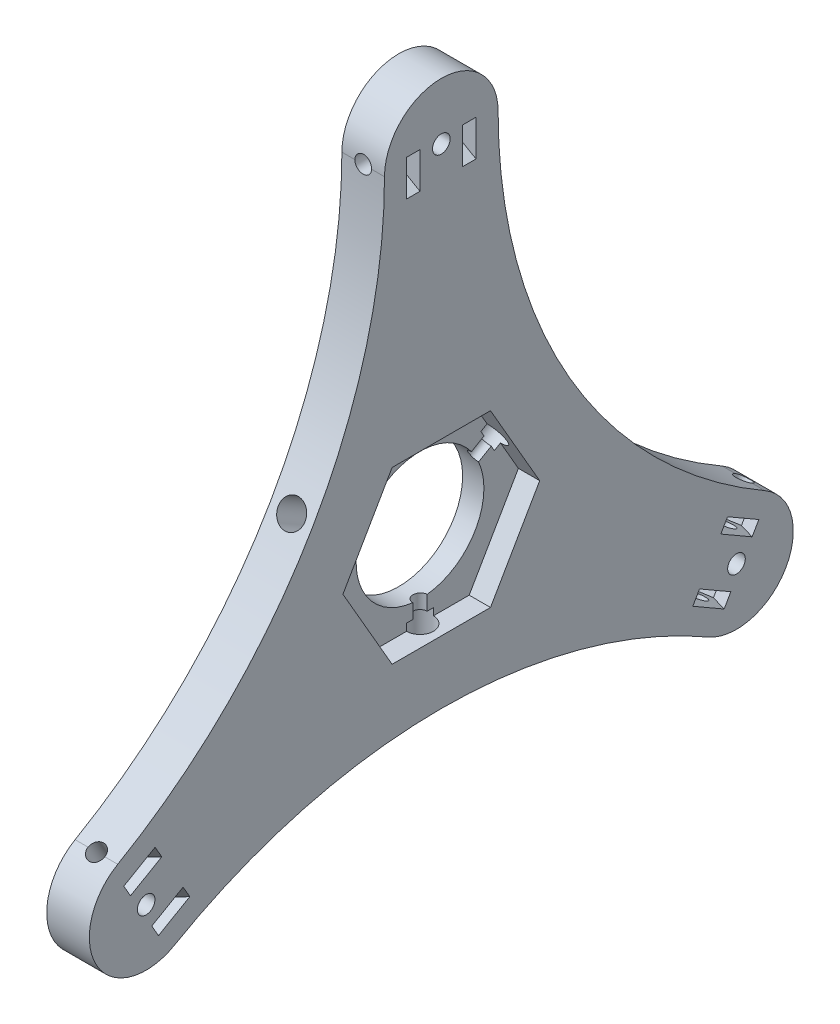
SolidWorks part; units mm, degrees
ref_plane "Front Plane" through (0, 0, 0) normal (0, 0, 1) x (1, 0, 0)
ref_plane "Top Plane" through (0, 0, 0) normal (0, 1, 0) x (1, 0, 0)
ref_plane "Right Plane" through (0, 0, 0) normal (1, 0, 0) x (0, 0, -1)
sketch "Sketch1" plane through (0, 0, 0) normal (1, 0, 0) x (0, 0, -1)
  line L0 (0, 0) -> (0, 76.2) construction
  line L1 (0, 0) -> (65.9911, -38.1) construction
  line L2 (0, 0) -> (-65.9911, -38.1) construction
  line L3 (-65.9911, -38.1) -> (0, 76.2) construction
  line L4 (0, 76.2) -> (65.9911, -38.1) construction
  line L5 (65.9911, -38.1) -> (-65.9911, -38.1) construction
  line L6 (-12.7, 76.2) -> (12.7, 76.2) construction
  line L8 (-3.6662, 6.35) -> (-7.3323, 0)
  line L9 (-7.3323, 0) -> (-3.6662, -6.35)
  line L10 (-3.6662, -6.35) -> (3.6662, -6.35)
  line L11 (3.6662, -6.35) -> (7.3323, 0)
  line L12 (7.3323, 0) -> (3.6662, 6.35)
  line L13 (3.6662, 6.35) -> (-3.6662, 6.35)
  circle A1 centre (0, 76.2) radius 1.9685
  circle A2 centre (65.9911, -38.1) radius 1.9685
  circle A3 centre (-65.9911, -38.1) radius 1.9685
  arc A4 (12.7, 76.2) -> (-12.7, 76.2) centre (0, 76.2) ccw
  arc A5 (59.6411, -49.0985) -> (72.3411, -27.1015) centre (65.9911, -38.1) ccw
  arc A6 (-72.3411, -27.1015) -> (-59.6411, -49.0985) centre (-65.9911, -38.1) ccw
  arc A7 (-12.7, 76.2) -> (-72.3411, -27.1015) centre (-131.9823, 76.2) cw
  arc A8 (12.7, 76.2) -> (72.3411, -27.1015) centre (131.9823, 76.2) ccw
  arc A9 (-59.6411, -49.0985) -> (59.6411, -49.0985) centre (0, -152.4) cw
  circle A10 centre (0, 0) radius 6.35 construction
  dimension "D1" = 12.7
  dimension "D2" = 3.937
  dimension "D4" = 25.4
  dimension "D3" = 76.2
extrude "Boss-Extrude1" add sketch "Sketch1" along normal blind 9.525 contours A6 A9 A5 A8 A4 A7 A1 A2 A3 region at (0, 15.5067, -26.8583)
sketch "Sketch3" plane through (0, 3.175, 5.4993) normal (0, -0.5, -0.866) x (-1, 0, 0)
  line L0 (-9.525, 0) -> (0, 0) construction
  line L4 (0, -3.6662) -> (0, 3.6662)
  line L5 (0, 3.6662) -> (-9.525, 3.6662)
  line L6 (-9.525, 3.6662) -> (-9.525, -3.6662)
  line L7 (-9.525, -3.6662) -> (0, -3.6662)
  line L8 (0, -3.6662) -> (0, 3.6662) construction
  line L9 (0, 3.6662) -> (-9.525, 3.6662) construction
  line L10 (-9.525, 3.6662) -> (-9.525, -3.6662) construction
  line L11 (-9.525, -3.6662) -> (0, -3.6662) construction
  circle A0 centre (-4.7625, 0) radius 1.6
  dimension "D2" = 3.2
  dimension "D1" = 0
extrude "Cut-Extrude1" cut sketch "Sketch3" against normal through all
sketch "Sketch5" plane through (0, 3.175, 5.4993) normal (0, -0.5, -0.866) x (-1, 0, 0)
  circle A0 centre (-4.7625, 0) radius 3
  dimension "D1" = 6
extrude "Cut-Extrude3" cut sketch "Sketch5" against normal through all from offset 11.1125 offset against normal yes
ref_axis "Axis1" through (-0.4763, 0, 0) along (1, 0, 0)
pattern_circular "CirPattern9" count 3 over 360 about axis through (-0.4763, 0, 0) along (1, 0, 0) of "Cut-Extrude3", "Cut-Extrude1"
sketch "Sketch4" plane through (0, 3.175, 5.4993) normal (0, -0.5, -0.866) x (-1, 0, 0)
  line L0 (-9.525, 0) -> (0, 0) construction
  line L1 (-3.1748, 2.75) -> (-6.3502, 2.75)
  line L2 (-6.3502, 2.75) -> (-7.9379, 0) construction
  line L3 (-7.9379, 0) -> (-6.3502, -2.75) construction
  line L4 (-6.3502, -2.75) -> (-3.1748, -2.75)
  line L5 (-3.1748, -2.75) -> (-1.5871, 0)
  line L6 (-1.5871, 0) -> (-3.1748, 2.75)
  line L7 (-6.3502, 2.75) -> (-9.525, 2.75)
  line L8 (-9.525, 3.6662) -> (-9.525, -3.6662) construction
  line L9 (-9.525, 2.75) -> (-9.525, -2.75)
  line L10 (-9.525, -2.75) -> (-6.3502, -2.75)
  circle A0 centre (-4.7625, 0) radius 2.75 construction
  dimension "D1" = 5.5
extrude "Cut-Extrude2" cut sketch "Sketch4" against normal blind 3.2 from offset 3.175 offset against normal yes
sketch "Sketch6" plane through (0, 0, 0) normal (0, 0, 1) x (1, 0, 0)
  line L0 (9.525, 76.2) -> (0, 76.2) construction
  line L1 (9.525, 74.2315) -> (9.525, 78.1685) construction
  line L2 (9.525, 74.2315) -> (9.525, 78.1685) construction
  line L3 (4.7625, 88.9) -> (4.7625, 71.7991) construction
  line L4 (9.525, 88.9) -> (0, 88.9) construction
  circle A0 centre (4.7625, 76.2) radius 1.875
  dimension "D1" = 3.75
extrude "Cut-Extrude4" cut sketch "Sketch6" against normal through all
sketch "Sketch7" plane through (0, 0, 0) normal (0, 0, 1) x (1, 0, 0)
  line L0 (8.2625, 78.2207) -> (9.525, 77.4918)
  line L1 (1.2625, 74.1793) -> (4.7625, 72.1585)
  line L2 (4.7625, 72.1585) -> (8.2625, 74.1793) construction
  line L3 (8.2625, 74.1793) -> (8.2625, 78.2207) construction
  line L4 (8.2625, 78.2207) -> (4.7625, 80.2415)
  line L5 (4.7625, 80.2415) -> (1.2625, 78.2207)
  line L6 (1.2625, 78.2207) -> (1.2625, 74.1793)
  line L7 (9.525, 74.2315) -> (9.525, 78.1685) construction
  line L8 (9.525, 77.4918) -> (9.525, 69.4089)
  line L9 (9.525, -27.1015) -> (9.525, 76.2) construction
  line L10 (4.7625, 72.1585) -> (9.525, 69.4089)
  circle A0 centre (4.7625, 76.2) radius 3.5 construction
  dimension "D1" = 7
extrude "Cut-Extrude5" cut sketch "Sketch7" against normal blind 3 from offset 4.7625 offset against normal yes
mirror "Mirror1" about plane through (0, 0, 0) normal (0, 0, 1) of "Cut-Extrude5", "Cut-Extrude4"
pattern_circular "CirPattern1" count 3 over 360 about axis through (-0.4763, 0, 0) along (1, 0, 0) of "Cut-Extrude5", "Mirror1"
sketch "Sketch8" plane through (9.525, 0, 0) normal (1, 0, 0) x (0, 0, -1)
  circle A0 centre (0, 0) radius 14.2875
  dimension "D1" = 28.575
extrude "Cut-Extrude6" cut sketch "Sketch8" against normal through all
sketch "Sketch9" plane through (9.525, 0, 0) normal (1, 0, 0) x (0, 0, -1)
  line L1 (-10.9985, 19.05) -> (-21.997, 0)
  line L2 (-21.997, 0) -> (-10.9985, -19.05)
  line L3 (-10.9985, -19.05) -> (10.9985, -19.05)
  line L4 (10.9985, -19.05) -> (21.997, 0)
  line L5 (21.997, 0) -> (10.9985, 19.05)
  line L6 (10.9985, 19.05) -> (-10.9985, 19.05)
  circle A0 centre (0, 0) radius 19.05 construction
  dimension "D1" = 38.1
extrude "Cut-Extrude7" cut sketch "Sketch9" against normal blind 4.7625
